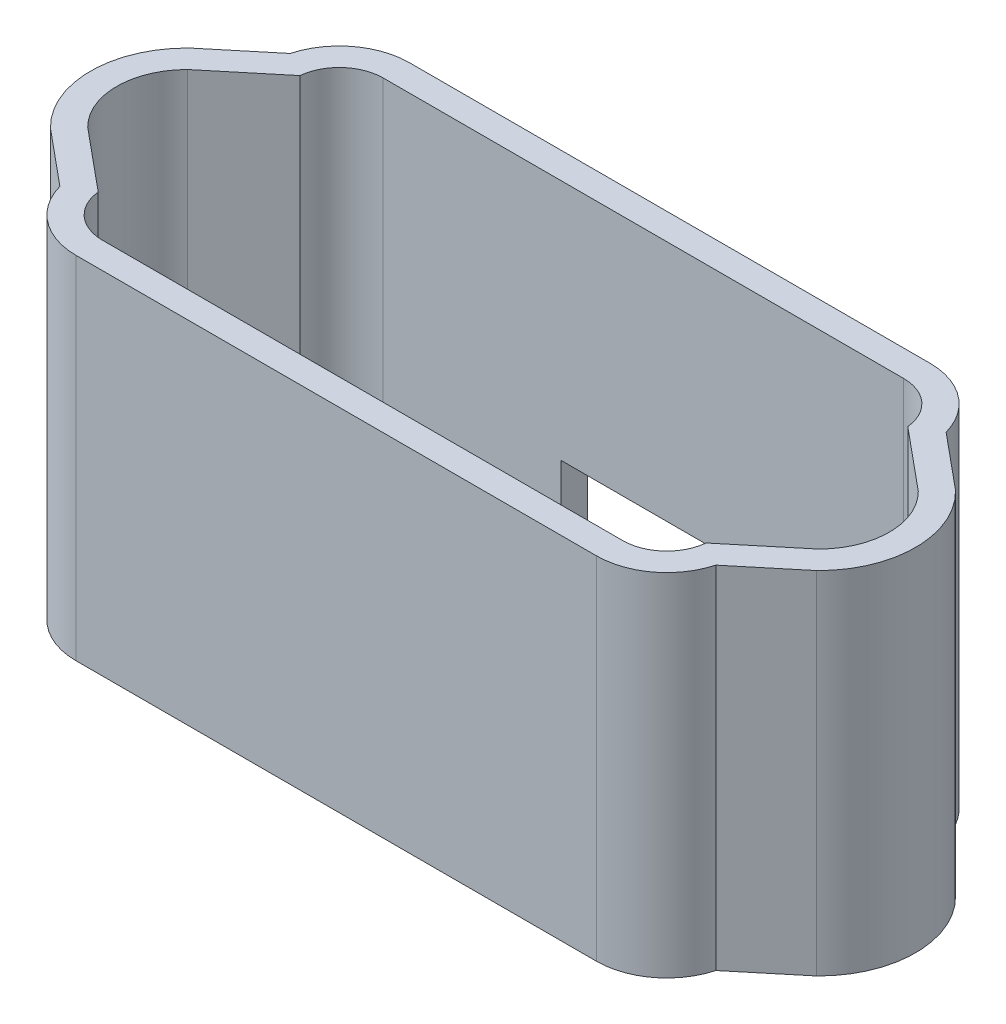
SolidWorks part; units mm, degrees
ref_plane "Front Plane" through (0, 0, 0) normal (0, 0, 1) x (1, 0, 0)
ref_plane "Top Plane" through (0, 0, 0) normal (0, 1, 0) x (1, 0, 0)
ref_plane "Right Plane" through (0, 0, 0) normal (1, 0, 0) x (0, 0, -1)
sketch "Sketch1" plane through (0, 0, 0) normal (0, 1, 0) x (1, 0, 0)
  line L12 (-30.7589, 43.3489) -> (-30.7589, 48.3489) construction
  line L13 (-21.7589, 43.3489) -> (-30.7589, 43.3489) construction
  line L14 (-21.7589, 48.3489) -> (-21.7589, 43.3489) construction
  line L15 (-11.4339, 48.3489) -> (-21.7589, 48.3489)
  line L16 (-5.784, 43.3238) -> (-9.4339, 46.3489)
  line L17 (-9.4339, 35.3489) -> (-5.784, 38.3741)
  line L18 (-41.0839, 33.3489) -> (-11.4339, 33.3489)
  line L19 (-46.7337, 38.3741) -> (-43.0839, 35.3489)
  line L20 (-43.0839, 46.3489) -> (-46.7337, 43.3238)
  line L21 (-30.7589, 48.3489) -> (-41.0839, 48.3489)
  line L22 (-21.7589, 48.3489) -> (-30.7589, 48.3489)
  line L23 (-21.7589, 50.3489) -> (-30.7589, 50.3489)
  line L24 (-30.7589, 50.3489) -> (-41.0839, 50.3489)
  line L25 (-44.9414, 47.407) -> (-48.0738, 44.8108)
  line L26 (-48.0738, 36.8871) -> (-44.9414, 34.2909)
  line L27 (-41.0839, 31.3489) -> (-11.4339, 31.3489)
  line L28 (-7.5763, 34.2909) -> (-4.4439, 36.8871)
  line L29 (-4.4439, 44.8108) -> (-7.5763, 47.407)
  line L30 (-11.4339, 50.3489) -> (-21.7589, 50.3489)
  arc A0 (-9.4339, 46.3489) -> (-11.4339, 48.3489) centre (-11.4339, 46.3489) ccw
  arc A1 (-5.784, 38.3741) -> (-5.784, 43.3238) centre (-8.2589, 40.8489) ccw
  arc A2 (-11.4339, 33.3489) -> (-9.4339, 35.3489) centre (-11.4339, 35.3489) ccw
  arc A3 (-43.0839, 35.3489) -> (-41.0839, 33.3489) centre (-41.0839, 35.3489) ccw
  arc A4 (-46.7337, 43.3238) -> (-46.7337, 38.3741) centre (-44.2589, 40.8489) ccw
  arc A5 (-41.0839, 48.3489) -> (-43.0839, 46.3489) centre (-41.0839, 46.3489) ccw
  arc A6 (-41.0839, 50.3489) -> (-44.9414, 47.407) centre (-41.0839, 46.3489) ccw
  arc A7 (-48.0738, 44.8108) -> (-48.0738, 36.8871) centre (-44.2589, 40.8489) ccw
  arc A8 (-44.9414, 34.2909) -> (-41.0839, 31.3489) centre (-41.0839, 35.3489) ccw
  arc A9 (-11.4339, 31.3489) -> (-7.5763, 34.2909) centre (-11.4339, 35.3489) ccw
  arc A10 (-4.4439, 36.8871) -> (-4.4439, 44.8108) centre (-8.2589, 40.8489) ccw
  arc A11 (-7.5763, 47.407) -> (-11.4339, 50.3489) centre (-11.4339, 46.3489) ccw
  dimension "D4" = 3.5
  dimension "D6" = 8.2589
  dimension "D8" = 30.7589
  dimension "D3" = 2
  dimension "D1" = 33.3489
  dimension "D2" = 11.4339
  dimension "D5" = 5.784
  dimension "D7" = 21.7589
  dimension "D9" = 38.3741
  dimension "D10" = 2
  dimension "D12" = 43.3489
extrude "Boss-Extrude1" add sketch "Sketch1" along normal blind 1 contours L22 L21 A5 L20 A4 L19 A3 L18 A2 L17 A1 L16 A0 L15
extrude "Boss-Extrude2" add sketch "Sketch1<3>" along normal blind 20
sketch "Sketch1<3>" plane through (0, 0, 0) normal (0, 1, 0) x (1, 0, 0) same geometry as "Sketch1"
sketch "Sketch2" plane through (0, 0, -50.3489) normal (0, 0, 1) x (1, 0, 0)
  line L0 (-26.2589, 1) -> (-21.7589, 1) construction
  line L1 (-11.4339, 1) -> (-41.0839, 1) construction
  line L2 (-21.7589, 1) -> (-21.7589, 6)
  line L3 (-21.7589, 8) -> (-30.7589, 8) construction
  line L4 (-30.7589, 6) -> (-30.7589, 1)
  line L5 (-30.7589, 1) -> (-26.2589, 1) construction
  line L6 (-30.7589, 1) -> (-30.7589, 0)
  line L7 (-11.4339, 0) -> (-41.0839, 0) construction
  line L8 (-30.7589, 0) -> (-21.7589, 0)
  line L9 (-21.7589, 0) -> (-21.7589, 1)
  line L10 (-21.7589, 6) -> (-26.2589, 8) construction
  line L11 (-26.2589, 8) -> (-30.7589, 6) construction
  line L12 (-21.7589, 6) -> (-30.7589, 6)
  point P8 (-26.2589, 8)
  point P20 (-26.2589, 0)
  dimension "D1" = 9
  dimension "D2" = 7
  dimension "D3" = 5
  dimension "D4" = 9
extrude "Cut-Extrude1" cut sketch "Sketch2" along normal up to surface (2 mm away) up to face at (-26.2589, 10.5, -48.3489)
sketch "Sketch3" plane through (0, 1, 0) normal (0, 1, 0) x (1, 0, 0)
  circle A0 centre (-8.2589, 40.8489) radius 1.175
  circle A1 centre (-44.2589, 40.8489) radius 1.175
  dimension "D1" = 2.35
extrude "Cut-Extrude2" cut sketch "Sketch3" against normal blind 20
other "Move Face1" flip direction yes face at (-26.2589, 6, -49.3489) face at (-30.7589, 2.6, -49.1489) face at (-21.7589, 2.6, -49.1489) face at (-44.2589, 1, -39.6739) face at (-8.2589, 1, -39.6739) offset 0.2 parameters "D1"=0.2
other "Move Face2" flip direction yes face at (-7.6089, 10.5, -44.8364) face at (-10.2268, 10.5, -47.5561) face at (-26.2589, 7.05, -48.3489) face at (-42.291, 10.5, -47.5561) face at (-44.9088, 10.5, -44.8364) face at (-47.2463, 10.5, -40.8489) face at (-44.9088, 10.5, -36.8615) face at (-42.291, 10.5, -34.1418) face at (-26.2589, 10.5, -33.3489) face at (-10.2268, 10.5, -34.1418) face at (-7.6089, 10.5, -36.8615) face at (-5.2714, 10.5, -40.8489) offset 0.5 parameters "D1"=0.5
